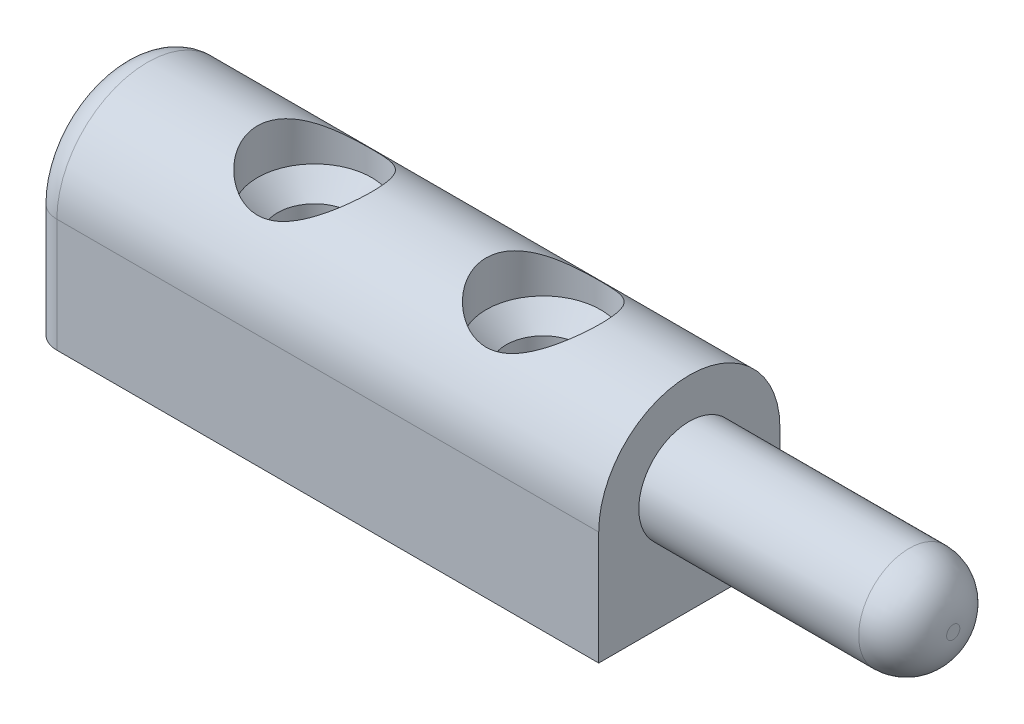
SolidWorks part; units mm, degrees
ref_plane "Plano frontal" through (0, 0, 0) normal (0, 0, 1) x (1, 0, 0)
ref_plane "Plano superior" through (0, 0, 0) normal (0, 1, 0) x (1, 0, 0)
ref_plane "Plano direito" through (0, 0, 0) normal (1, 0, 0) x (0, 0, -1)
sketch "Esboço1" plane through (0, 0, 0) normal (1, 0, 0) x (0, 0, -1)
  line L0 (0, 5.15) -> (0, -6.4502) construction
  line L1 (5.15, -6.4502) -> (-5.15, -6.4502)
  line L2 (-5.15, -6.4502) -> (-5.15, 0)
  line L3 (5.15, -6.4502) -> (5.15, 0)
  circle A0 centre (0, 0) radius 2.95
  arc A1 (5.15, 0) -> (-5.15, 0) centre (0, 0) ccw
  circle A2 centre (0, 0) radius 5.15 construction
  dimension "D1" = 5.9
  dimension "D3" = 11.6002
  dimension "D2" = 2.2
extrude "Ressalto-extrusão1" add sketch "Esboço1" along normal mid plane 32.3
sketch "Esboço2" plane through (-16.15, 0, 0) normal (-1, 0, 0) x (0, 0, 1)
  line L3 (-5.15, 0) -> (-5.15, -6.4502)
  line L4 (-5.15, -6.4502) -> (5.15, -6.4502)
  line L5 (5.15, -6.4502) -> (5.15, 0)
  line L6 (-5.15, 0) -> (-5.15, -6.4502)
  line L7 (-5.15, -6.4502) -> (5.15, -6.4502)
  line L8 (5.15, -6.4502) -> (5.15, 0)
  arc A1 (5.15, 0) -> (-5.15, 0) centre (0, 0) ccw
  arc A2 (5.15, 0) -> (-5.15, 0) centre (0, 0) ccw
  dimension "D1" = 0
extrude "Ressalto-extrusão2" add sketch "Esboço2" against normal through all
fillet "Filete1" radius 1.5 3 edges at (-16.15, -3.2251, -5.15) (-16.15, -3.2251, 5.15) (-16.15, 5.15, 0)
sketch "Esboço3" plane through (0, -6.4502, 0) normal (0, -1, 0) x (1, 0, 0)
  line L0 (-16.15, 0) -> (-5.15, 0) construction
  line L1 (-16.15, 3.65) -> (-16.15, -3.65) construction
  circle A0 centre (-5.15, 0) radius 3.25
  circle A1 centre (7.85, 0) radius 3.25
  dimension "D1" = 6.5
  dimension "D3" = 11
  dimension "D2" = 2
extrude "Corte-extrusão1" cut sketch "Esboço3" against normal through all
sketch "Esboço5" plane through (0, -6.4502, 0) normal (0, -1, 0) x (1, 0, 0)
  circle A0 centre (-5.15, 0) radius 2.1
  circle A1 centre (7.85, 0) radius 2.1
  circle A3 centre (7.85, 0) radius 3.25
  circle A4 centre (-5.15, 0) radius 3.25 construction
  circle A5 centre (-5.15, 0) radius 3.25
  dimension "D1" = 4.2
  dimension "D2" = 2
extrude "Ressalto-extrusão3" add sketch "Esboço5" against normal blind 9.1
chamfer "Chanfro1" distance 1.2 angle 45 2 edges at (-5.15, 2.6498, -2.1) (7.85, 2.6498, -2.1)
sketch "Esboço7" plane through (16.15, 0, 0) normal (1, 0, 0) x (0, 0, -1)
  circle A2 centre (0, 0) radius 2.875
  dimension "D1" = 5.75
extrude "Ressalto-extrusão6" add sketch "Esboço7" along normal blind 15
fillet "Filete2" radius 2.5 1 edges at (31.15, 0, -2.875)
